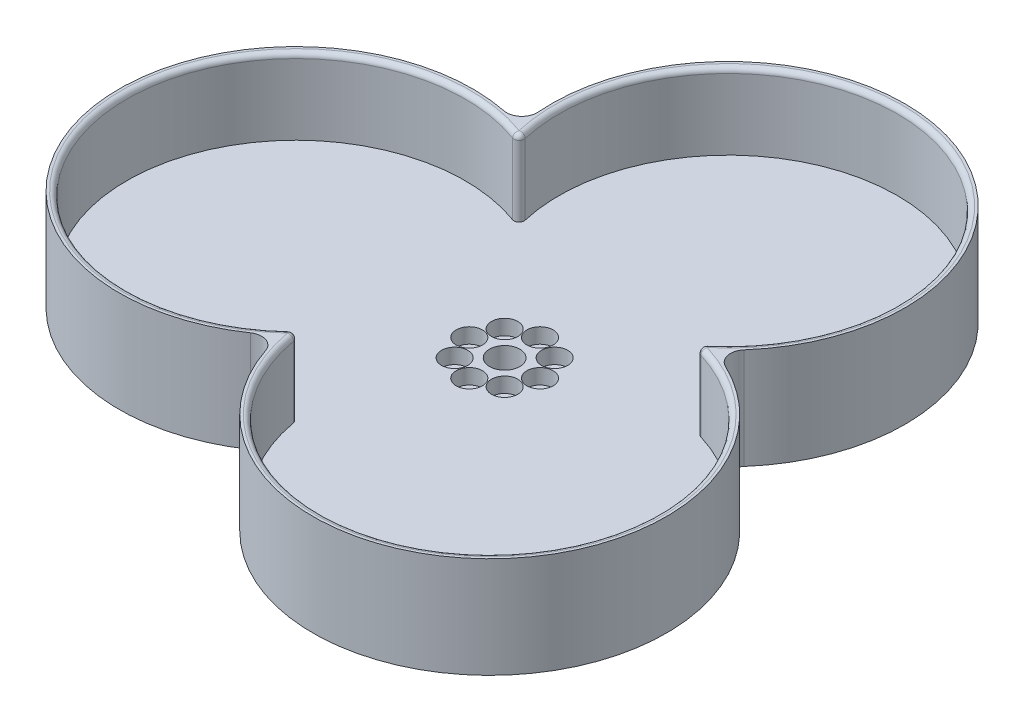
SolidWorks part; units mm, degrees
ref_plane "前视基准面" through (0, 0, 0) normal (0, 0, 1) x (1, 0, 0)
ref_plane "上视基准面" through (0, 0, 0) normal (0, 1, 0) x (1, 0, 0)
ref_plane "右视基准面" through (0, 0, 0) normal (1, 0, 0) x (0, 0, -1)
other "Configuration Table"
sketch "草图1" plane through (0, 0, 0) normal (0, 1, 0) x (1, 0, 0)
  line L0 (0, 0) -> (-15, 0) construction
  line L1 (0, 0) -> (7.5, 12.9904) construction
  line L2 (0, 0) -> (7.5, -12.9904) construction
  circle A0 centre (0, 0) radius 15
  circle A1 centre (0, 0) radius 7 construction
  circle A2 centre (0, 7) radius 1.5
  circle A3 centre (4.9497, 4.9497) radius 1.5
  circle A4 centre (7, 0) radius 1.5
  circle A5 centre (4.9497, -4.9497) radius 1.5
  circle A6 centre (0, -7) radius 1.5
  circle A7 centre (-4.9497, -4.9497) radius 1.5
  circle A8 centre (-7, 0) radius 1.5
  circle A9 centre (-4.9497, 4.9497) radius 1.5
  circle A10 centre (0, 0) radius 3
  point P22 (0, 0)
  point P34 (0, 0)
  point P37 (0, 0)
  dimension "D1" = 30
  dimension "D2" = 14
  dimension "D3" = 3
  dimension "D5" = 6
  dimension "D9" = 3
  dimension "D4" = 8
extrude "凸台-拉伸1" add sketch "草图1" along normal blind 3
sketch "草图2" plane through (0, 3, 0) normal (0, 1, 0) x (1, 0, 0)
  line L1 (3.8891, -3.8891) -> (6.0104, -6.0104) construction
  line L2 (3.6813, -4.149) -> (5.5938, -6.3044) construction
  circle A34 centre (4.9497, -4.9497) radius 1.5 construction
  circle A36 centre (-4.9497, 4.9497) radius 1.5
  circle A37 centre (-4.9497, 4.9497) radius 1.5
  circle A38 centre (-4.9497, -4.9497) radius 1.5
  circle A39 centre (-4.9497, -4.9497) radius 1.5
  circle A40 centre (0, -7) radius 1.5
  circle A41 centre (0, -7) radius 1.5
  circle A42 centre (0, 0) radius 3
  circle A43 centre (0, 0) radius 3
  circle A44 centre (-7, 0) radius 1.5
  circle A45 centre (-7, 0) radius 1.5
  circle A46 centre (7, 0) radius 1.5 construction
  circle A47 centre (4.9497, 4.9497) radius 1.5 construction
  circle A48 centre (0, 7) radius 1.5 construction
  circle A49 centre (4.9497, -4.9497) radius 1.5
  circle A50 centre (7, 0) radius 1.5
  circle A51 centre (4.9497, 4.9497) radius 1.5
  circle A52 centre (0, 7) radius 1.5
  arc A54 (34.2873, 7.027) -> (-23.2292, 26.1802) centre (11.0581, 33.2072) ccw
  arc A55 (-11.0581, -33.2072) -> (34.2873, 7.027) centre (23.2292, -26.1802) ccw
  arc A57 (-23.2292, 26.1802) -> (-11.0581, -33.2072) centre (-34.2873, -7.027) ccw
  point P28 (0, 0)
  dimension "D2" = 0
  dimension "D4" = 0
  dimension "D1" = 0
  dimension "D3" = 0
  dimension "D6" = 35
  dimension "D7" = 35
  dimension "D5" = 0
extrude "凸台-拉伸2" add sketch "草图2" along normal blind 5
sketch "草图5" plane through (0, 8, 0) normal (0, 1, 0) x (1, 0, 0)
  circle A0 centre (0, 7) radius 2.6
  circle A1 centre (4.9497, 4.9497) radius 2.6
  circle A2 centre (7, 0) radius 2.6
  circle A3 centre (4.9497, -4.9497) radius 2.6
  circle A4 centre (0, -7) radius 2.6
  circle A5 centre (-4.9497, -4.9497) radius 2.6
  circle A6 centre (-7, 0) radius 2.6
  circle A7 centre (-4.9497, 4.9497) radius 2.6
  dimension "D1" = 5.2
  dimension "D2" = 5.2
  dimension "D3" = 5.2
  dimension "D4" = 5.2
  dimension "D5" = 5.2
  dimension "D6" = 5.2
  dimension "D7" = 5.2
  dimension "D8" = 5.2
extrude "切除-拉伸1" cut sketch "草图5" against normal blind 3 contours A0 | A1 | A2 | A3 | A4 | A5 | A6 | A7
sketch "草图3" plane through (0, 8, 0) normal (0, 1, 0) x (1, 0, 0)
  arc A70 (31.1185, 6.3775) -> (-21.0824, 23.7607) centre (11.0581, 33.2072) ccw
  arc A72 (-10.0362, -30.1382) -> (31.1185, 6.3775) centre (23.2292, -26.1802) ccw
  arc A77 (-21.0824, 23.7607) -> (-10.0362, -30.1382) centre (-34.2873, -7.027) ccw
  arc A79 (34.2873, 7.027) -> (-23.2292, 26.1802) centre (11.0581, 33.2072) ccw
  arc A80 (-11.0581, -33.2072) -> (34.2873, 7.027) centre (23.2292, -26.1802) ccw
  arc A81 (-23.2292, 26.1802) -> (-11.0581, -33.2072) centre (-34.2873, -7.027) ccw
  arc A82 (34.2873, 7.027) -> (-23.2292, 26.1802) centre (11.0581, 33.2072) ccw construction
  point P10 (0, 0)
  point P12 (0, 0)
  point P13 (0, 0)
  point P21 (0, 0)
  point P23 (0, 0)
  point P24 (0, 0)
  point P26 (0, 0)
  point P28 (0, 0)
  point P36 (0, 0)
  dimension "D1" = 33.5
  dimension "D2" = 33.5
  dimension "D3" = 35
  dimension "D4" = 35
  dimension "D5" = 35
  dimension "D6" = 33.5
extrude "凸台-拉伸3" add sketch "草图3" along normal blind 15 contours A72 A70 A77
fillet "圆角5" radius 1 3 edges at (-10.0362, 15.5, 30.1382) (31.1185, 15.5, -6.3775) (-21.0824, 15.5, -23.7607)
fillet "圆角6" radius 1 6 edges at (-21.8867, 23, -24.6672) (32.3058, 23, -6.6209) (-10.4191, 23, 31.2881) (45.4629, 23, 51.2384) (21.6424, 23, -64.9912) (-67.1052, 23, 13.7528)
fillet "圆角7" radius 3 3 edges at (-23.2292, 13, -26.1802) (34.2873, 13, -7.027) (-11.0581, 13, 33.2072)
